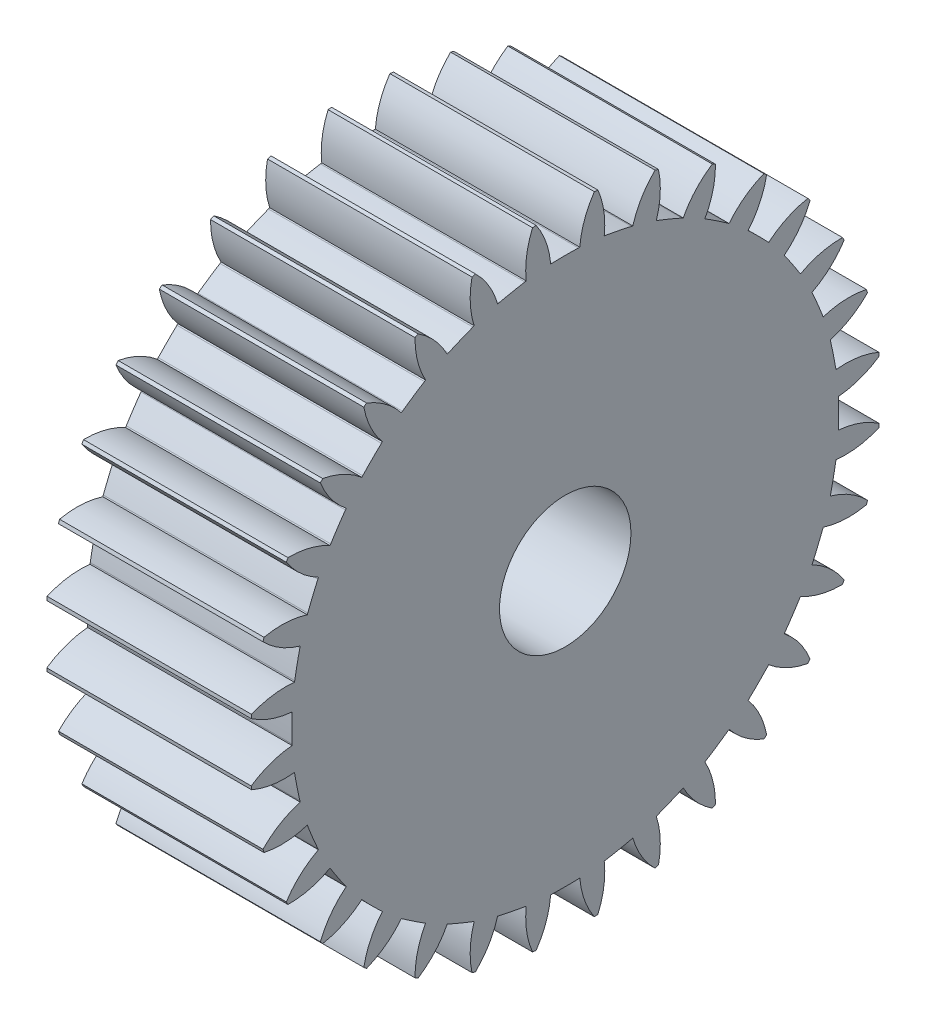
SolidWorks part; units mm, degrees
ref_plane "Front Plane" through (0, 0, 0) normal (0, 0, 1) x (1, 0, 0)
ref_plane "Top Plane" through (0, 0, 0) normal (0, 1, 0) x (1, 0, 0)
ref_plane "Right Plane" through (0, 0, 0) normal (1, 0, 0) x (0, 0, -1)
sketch "Sketch1" plane through (0, 0, 0) normal (1, 0, 0) x (0, 0, -1)
  circle A0 centre (0, 0) radius 107.95
  dimension "D1" = 215.9
extrude "Boss-Extrude1" add sketch "Sketch1" along normal mid plane 70
sketch "Sketch6" plane through (35, 0, 0) normal (1, 0, 0) x (0, 0, -1)
  circle A0 centre (0, 0) radius 22.5
  dimension "D1" = 45
extrude "Cut-Extrude4" cut sketch "Sketch6" against normal through all
sketch "Sketch7" plane through (35, 0, 0) normal (1, 0, 0) x (0, 0, -1)
  line L0 (0, 0) -> (0, 187.3) construction
  line L1 (0, 93.65) -> (-4.985, 93.5172)
  line L2 (0, 93.65) -> (4.985, 93.5172)
  line L3 (-9.975, 107.4881) -> (0, 118.9322)
  line L4 (9.975, 107.4881) -> (0, 118.9322)
  circle A0 centre (0, 0) radius 93.65 construction
  circle A1 centre (0, 0) radius 101.6 construction
  arc A2 (-4.985, 93.5172) -> (-9.975, 107.4881) centre (-33.831, 91.0909) ccw
  circle A3 centre (0, 0) radius 107.95 construction
  arc A4 (4.985, 93.5172) -> (9.975, 107.4881) centre (33.831, 91.0909) cw
  dimension "D1" = 203.2
  dimension "D2" = 187.3
  dimension "D3" = 4.99
  dimension "D4" = 19.95
extrude "Cut-Extrude5" cut sketch "Sketch7" against normal through all
fillet "Fillet1" radius 170 1 edges at (0, 93.65, 0)
pattern_circular "CirPattern1" count 32 over 360 about axis through (35, 0, 0) along (1, 0, 0) of "Fillet1", "Cut-Extrude5"
